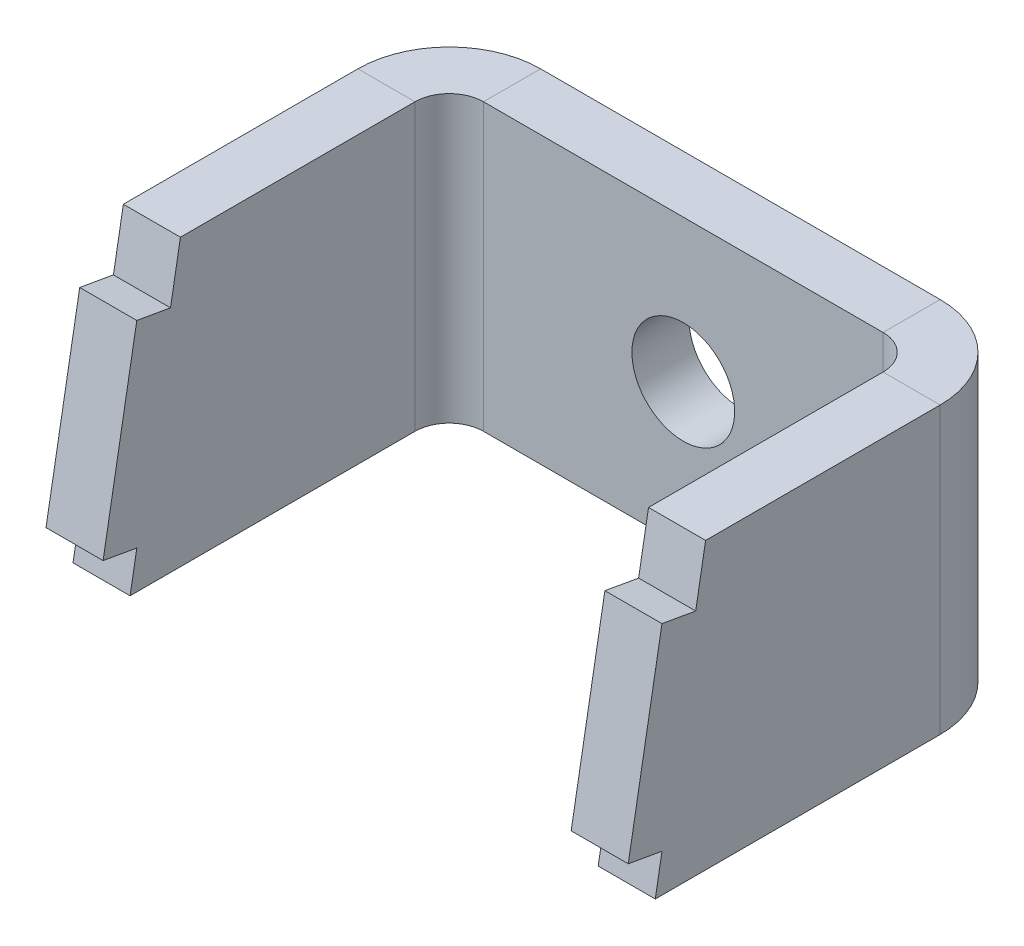
SolidWorks part; units mm, degrees
note: The reader was unsure of these and kept them because the rebuilt part matched: thickness of "Базовая кромка1", "Ребро-кромка1", "Ребро-кромка2", "Листовой металл1", "Листовой металл8", "Листовой металл9", "Листовой металл10", "Листовой металл11", "Листовой металл12"; flange length of "Ребро-кромка1", "Ребро-кромка2".
ref_plane "Спереди" through (0, 0, 0) normal (0, 0, 1) x (1, 0, 0)
ref_plane "Сверху" through (0, 0, 0) normal (0, 1, 0) x (1, 0, 0)
ref_plane "Справа" through (0, 0, 0) normal (1, 0, 0) x (0, 0, -1)
sketch "Эскиз1" plane through (0, 0, 0) normal (0, 0, 1) x (1, 0, 0)
  line L5 (0, 0) -> (0, -50000) construction
  line L6 (-17.5, 0) -> (17.5, 0)
  line L7 (-17.5, 0) -> (-17.5, 25)
  line L9 (17.5, 25) -> (-17.5, 25)
  line L10 (17.5, 0) -> (17.5, 25)
  point P0 (0, 0)
  dimension "D3" = 25
  dimension "D4" = 35
base flange "Базовая кромка1" sketch "Эскиз1" thickness 5 reverse thickness direction no parameters "D1"=3
edge flange "Ребро-кромка1" sketch "Эскиз29" flange angle 90 flange length 36 flange position bend outside bend radius 3 thickness 5 relief rectangular parameters "D6"=10
sketch "Эскиз29" plane through (-17.5, 0, 0) normal (1, 0, 0) x (0, 1, 0)
  line L2 (0, 0) -> (0, 31)
  line L3 (0, 31) -> (25, 31)
  line L4 (25, 31) -> (25, 0)
  line L5 (25, 0) -> (0, 0) construction
  line L6 (25, 0) -> (0, 0)
bend "EdgeBend1" bend radius 3 bend angle 90 parameters "D5"=1
edge flange "Ребро-кромка2" sketch "Эскиз32" flange angle 90 flange length 36 flange position bend outside bend radius 3 thickness 5 relief rectangular parameters "D6"=10
sketch "Эскиз32" plane through (17.5, 0, 0) normal (-1, 0, 0) x (0, -1, 0)
  line L2 (-25, 0) -> (-25, 31)
  line L3 (-25, 31) -> (0, 31)
  line L4 (0, 31) -> (0, 0)
  line L5 (0, 0) -> (-25, 0) construction
  line L6 (0, 0) -> (-25, 0)
bend "EdgeBend2" bend radius 3 bend angle 90 parameters "D5"=2
sketch "Эскиз33" plane through (25.5, 0, 0) normal (1, 0, 0) x (0, 0, -1)
  line L0 (-31, 0) -> (-31, 25)
  line L1 (-31, 25) -> (-26.5918, 25)
  line L2 (-26.5918, 25) -> (-31, 0)
  line L3 (-3, 0) -> (-31, 0) construction
  line L4 (-31, 0) -> (-31, 25) construction
  line L5 (-31, 25) -> (-3, 25) construction
  dimension "D1" = 10
  dimension "D2" = 100
extrude "Вырез-Вытянуть1" cut sketch "Эскиз33" against normal through all normal cut yes
sketch "Эскиз36" plane through (25.5, 0, 0) normal (1, 0, 0) x (0, 0, -1)
  line L0 (-26.5918, 25) -> (-27.3682, 20.5969)
  line L1 (-27.3682, 20.5969) -> (-24.4138, 20.076)
  line L2 (-24.4138, 20.076) -> (-23.5455, 25)
  line L3 (-23.5455, 25) -> (-26.5918, 25)
  line L4 (-24.4138, 20.076) -> (-29.0609, -6.2794) construction
  line L5 (-31, 0) -> (-26.5918, 25) construction
  line L6 (-26.5918, 25) -> (-3, 25) construction
  line L7 (-27.3658, 3.3342) -> (-30.3202, 3.8552)
  line L8 (-30.3202, 3.8552) -> (-31, 0)
  line L9 (-31, 0) -> (-27.9537, 0)
  line L10 (-27.9537, 0) -> (-27.3658, 3.3342)
  line L11 (-3, 0) -> (-31, 0) construction
  dimension "D1" = 3
  dimension "D2" = 5
  dimension "D3" = 17
extrude "Вырез-Вытянуть3" cut sketch "Эскиз36" against normal through all normal cut yes
sketch "Эскиз35" plane through (0, 0, -5) normal (0, 0, -1) x (-1, 0, 0)
  line L0 (17.5, 0) -> (-17.5, 0) construction
  circle A0 centre (0, 12.5) radius 4.5
  dimension "D1" = 9
  dimension "D2" = 12.5
extrude "Вырез-Вытянуть2" cut sketch "Эскиз35" against normal through all normal cut yes
sketch "Сгиб-Линии1" [suppressed] plane through (0, 0, 0) normal (0, 1, 0) x (1, 0, 0)
sketch "Граничная рамка1" [suppressed] plane through (0, 0, 0) normal (0, 1, 0) x (1, 0, 0)
sheet metal parameters "Листовой металл1" thickness 5 parameters "D1"=3
flat pattern "Развертка1" [suppressed]
sketch "Сгиб-Линии2" plane through (0, 0, 0) normal (0, 1, 0) x (1, 0, 0)
sketch3d "Граничная рамка2" [suppressed]
  line L0 (-25, 0, 0) -> (25, 0, 0) construction
  line L1 (-25, 30, 0) -> (25, 30, 0) construction
  line L2 (-25, 0, 0) -> (-25, 30, 0) construction
  line L3 (25, 0, 0) -> (25, 30, 0) construction
sheet metal parameters "Листовой металл8" thickness 5 parameters "D1"=3, "D7"=3
flat pattern "Развертка1"
sketch "Сгиб-Линии2" plane through (0, 0, 0) normal (0, 0, 1) x (1, 0, 0)
  line L0 (-29.3197, 30) -> (-29.3197, 0) construction
  line L1 (-29.3197, 30) -> (-29.3197, 0) construction
sketch3d "Граничная рамка2" [suppressed]
  line L0 (-75.6394, 0, 0) -> (25, 0, 0) construction
  line L1 (-75.6394, 30, 0) -> (25, 30, 0) construction
  line L2 (-75.6394, 0, 0) -> (-75.6394, 30, 0) construction
  line L3 (25, 0, 0) -> (25, 30, 0) construction
bend of the flat pattern "Плоское состояние-<EdgeBend1>1"
sheet metal parameters "Листовой металл9" thickness 5 parameters "D1"=3, "D7"=3
flat pattern "Развертка1"
sketch "Сгиб-Линии2" plane through (0, 0, 0) normal (0, 0, 1) x (1, 0, 0)
  line L0 (-29.3197, 30) -> (-29.3197, 0) construction
  line L1 (-29.3197, 30) -> (-29.3197, 0) construction
  line L2 (29.3197, 0) -> (29.3197, 30) construction
  line L3 (29.3197, 0) -> (29.3197, 30) construction
sketch3d "Граничная рамка2" [suppressed]
  line L0 (-75.6394, 0, 0) -> (75.6394, 0, 0) construction
  line L1 (-75.6394, 30, 0) -> (75.6394, 30, 0) construction
  line L2 (-75.6394, 0, 0) -> (-75.6394, 30, 0) construction
  line L3 (75.6394, 0, 0) -> (75.6394, 30, 0) construction
bend of the flat pattern "Плоское состояние-<EdgeBend1>1"
bend of the flat pattern "Плоское состояние-<EdgeBend2>1"
sheet metal parameters "Листовой металл10" thickness 5 parameters "D1"=3, "D7"=3
flat pattern "Развертка1"
sketch "Сгиб-Линии2" plane through (0, 0, 0) normal (0, 0, 1) x (1, 0, 0)
  line L0 (-24.3197, 25) -> (-24.3197, 0) construction
  line L1 (-24.3197, 25) -> (-24.3197, 0) construction
  line L2 (24.3197, 0) -> (24.3197, 25) construction
  line L3 (24.3197, 0) -> (24.3197, 25) construction
sketch3d "Граничная рамка2" [suppressed]
  line L0 (-70.6394, 0, 0) -> (70.6394, 0, 0) construction
  line L1 (-70.6394, 25, 0) -> (70.6394, 25, 0) construction
  line L2 (-70.6394, 0, 0) -> (-70.6394, 25, 0) construction
  line L3 (70.6394, 0, 0) -> (70.6394, 25, 0) construction
bend of the flat pattern "Плоское состояние-<EdgeBend1>1"
bend of the flat pattern "Плоское состояние-<EdgeBend2>1"
sheet metal parameters "Листовой металл11" thickness 5 parameters "D1"=3, "D7"=3
flat pattern "Развертка1"
sketch "Сгиб-Линии2" plane through (0, 0, 0) normal (0, 0, 1) x (1, 0, 0)
  line L0 (-21.8197, 25) -> (-21.8197, 0) construction
  line L1 (-21.8197, 25) -> (-21.8197, 0) construction
  line L2 (21.8197, 0) -> (21.8197, 25) construction
  line L3 (21.8197, 0) -> (21.8197, 25) construction
sketch3d "Граничная рамка2" [suppressed]
  line L0 (-53.4596, 0, 0) -> (53.4596, 0, 0) construction
  line L1 (-53.4596, 25, 0) -> (53.4596, 25, 0) construction
  line L2 (-53.4596, 0, 0) -> (-53.4596, 25, 0) construction
  line L3 (53.4596, 0, 0) -> (53.4596, 25, 0) construction
bend of the flat pattern "Плоское состояние-<EdgeBend1>1"
bend of the flat pattern "Плоское состояние-<EdgeBend2>1"
sheet metal parameters "Листовой металл12" thickness 5 parameters "D1"=3, "D7"=3
flat pattern "Развертка1"
sketch "Сгиб-Линии2" plane through (0, 0, 0) normal (0, 0, 1) x (1, 0, 0)
  line L0 (-24.3197, 25) -> (-24.3197, 0) construction
  line L1 (-24.3197, 25) -> (-24.3197, 0) construction
  line L2 (24.3197, 0) -> (24.3197, 25) construction
  line L3 (24.3197, 0) -> (24.3197, 25) construction
sketch3d "Граничная рамка2" [suppressed]
  line L0 (-70.6394, 0, 0) -> (70.6394, 0, 0) construction
  line L1 (-70.6394, 25, 0) -> (70.6394, 25, 0) construction
  line L2 (-70.6394, 0, 0) -> (-70.6394, 25, 0) construction
  line L3 (70.6394, 0, 0) -> (70.6394, 25, 0) construction
bend of the flat pattern "Плоское состояние-<EdgeBend1>1"
bend of the flat pattern "Плоское состояние-<EdgeBend2>1"
sheet metal parameters "Листовой металл13" thickness 3 parameters "D1"=3
flat pattern "Развертка13"
sketch "Сгиб-Линии3" plane through (0, 0, 0) normal (0, 1, 0) x (1, 0, 0)
sketch3d "Граничная рамка3" [suppressed]
  line L0 (35, 25, 0) -> (35, 0, 0) construction
  line L1 (38, 25, 0) -> (38, 0, 0) construction
  line L2 (35, 25, 0) -> (38, 25, 0) construction
  line L3 (35, 0, 0) -> (38, 0, 0) construction
